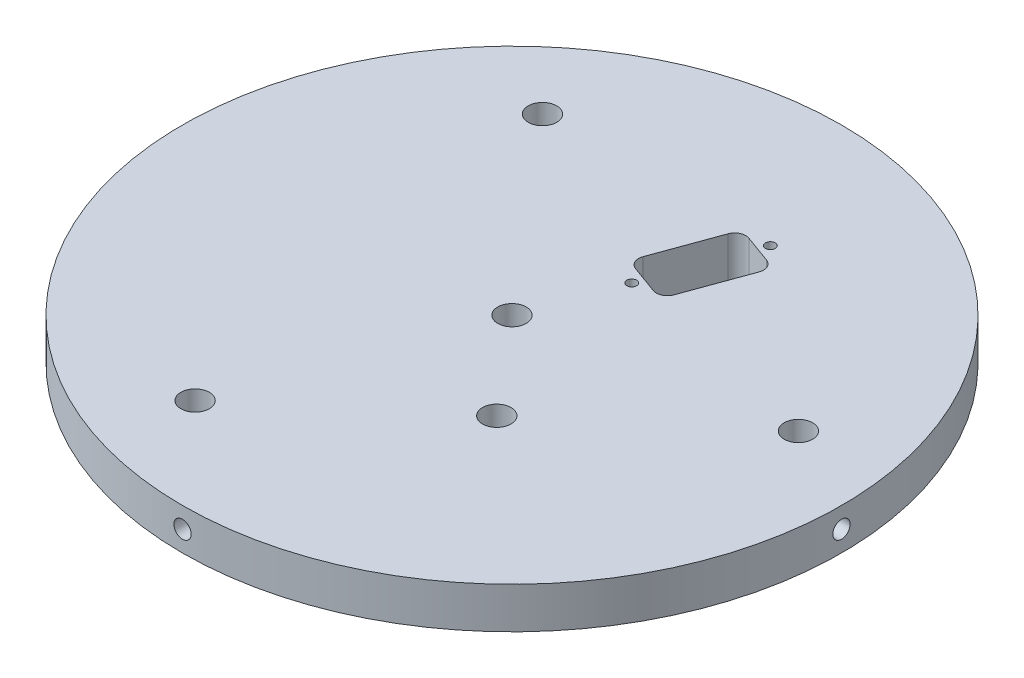
SolidWorks part; units mm, degrees
material "6061-T6 (SS)"
ref_plane "Front Plane" through (0, 0, 0) normal (0, 0, 1) x (1, 0, 0)
ref_plane "Top Plane" through (0, 0, 0) normal (0, 1, 0) x (1, 0, 0)
ref_plane "Right Plane" through (0, 0, 0) normal (1, 0, 0) x (0, 0, -1)
sketch "Sketch1" plane through (0, 0, 0) normal (0, 1, 0) x (1, 0, 0)
  line L0 (0, 0) -> (-50.3682, 60.0265)
  line L1 (0, 0) -> (50.3682, 60.0265)
  line L2 (0, 0) -> (0, 72.1431) construction
  circle A0 centre (0, 0) radius 78.359
  circle A1 centre (0, 0) radius 76.1746
  circle A2 centre (0, 0) radius 76.1746
  dimension "D1" = 156.718
  dimension "D2" = 152.3492
  dimension "D3" = 152.3492
  dimension "D4" = 80
extrude "Boss-Extrude1" add sketch "Sketch1" along normal blind 25.4 contours L2 A2 L1 A0 | L2 A1 L1 A2 | L2 A2 L1 A1 | L2 A0 L1 A2 | A2 L2 A1 L0 | A0 L2 A2 L0 | A2 L2 A0 L0 | A1 L2 A2 L0 region at (0, 0, 13.3592) region at (-23.5316, 0, -29.974) region at (-33.0764, 0, 70.9325) region at (-48.8794, 0, -59.85)
ref_plane "Plane1" through (0, 12.7, 0) normal (0, 1, 0) x (1, 0, 0)
sketch "Sketch6" plane through (0, 25.4, 0) normal (0, 1, 0) x (1, 0, 0)
  circle A0 centre (0, 0) radius 76.1746
  dimension "D1" = 152.3492
extrude "Boss-Extrude5" add sketch "Sketch6" along normal blind 9.525
sketch "Sketch7" plane through (0, 0, 0) normal (0, -1, 0) x (1, 0, 0)
  circle A0 centre (0, 0) radius 76.1746
  dimension "D1" = 152.3492
extrude "Boss-Extrude6" add sketch "Sketch7" along normal blind 9.525
sketch "Sketch8" plane through (0, -9.525, 0) normal (0, -1, 0) x (1, 0, 0)
  circle A0 centre (0, 0) radius 73.025
  dimension "D1" = 146.05
extrude "Cut-Extrude5" cut sketch "Sketch8" against normal up to surface (34.925 mm away) up to face at (0, 25.4, 76.1746)
ref_plane "Plane2" through (0, 0, -76.1746) normal (0, 0, -1) x (-1, 0, 0)
ref_plane "Plane5" through (0, 25.4, 0) normal (0, 1, 0) x (1, 0, 0)
ref_axis "Axis1" through (0, 0, 0) along (0, 1, 0)
sketch "Sketch3" plane through (0, 0, -76.1746) normal (0, 0, -1) x (-1, 0, 0)
  line L4 (76.1746, 0) -> (-76.1746, 0)
  line L5 (-76.1746, -9.525) -> (76.1746, -9.525)
  line L6 (76.1746, 25.4) -> (-76.1746, 25.4)
  line L7 (76.1746, 34.925) -> (-76.1746, 34.925)
  line L8 (0, 34.925) -> (0, 25.4) construction
  line L9 (0, 0) -> (0, -9.525) construction
  circle A0 centre (0, 30.1625) radius 2
  circle A1 centre (0, -4.7625) radius 2
  point P12 (0, 30.1625)
  point P13 (0, -4.7625)
  point P14 (-77.5445, 179.1871)
  dimension "D1" = 4
extrude "Cut-Extrude2" cut sketch "Sketch3" against normal blind 9.525 contours L8 A0 | L8 A0 | L9 A1 | L9 A1 region at (0, 30.1625, -76.1746) region at (0, -4.7625, -76.1746)
extrude "Cut-Extrude3" cut sketch "Sketch1<7>" against normal blind 9.525 from surface contours L2 A1 L1 A2 | A1 L2 A2 L0 | A2 L2 A0 L0 | L2 A2 L1 A0 region at (-23.5316, 0, -29.974) region at (-48.8794, 0, -59.85) starting at plane "Plane5"
sketch "Sketch1<7>" plane through (0, 0, 0) normal (0, 1, 0) x (1, 0, 0) same geometry as "Sketch1"
pattern_circular "CirPattern2" count 3 over 360 about axis through (0, 0, 0) along (0, 1, 0) of "Cut-Extrude3"
ref_plane "Plane3" through (0, 34.925, 0) normal (0, 1, 0) x (1, 0, 0)
sketch "Sketch4" plane through (0, 34.925, 0) normal (0, 1, 0) x (1, 0, 0)
  circle A0 centre (0, 0) radius 73.025
  dimension "D1" = 146.05
extrude "Boss-Extrude4" add sketch "Sketch4" against normal blind 9.525
pattern_circular "CirPattern3" count 4 over 360 about axis through (0, 0, 0) along (0, 1, 0) of "Cut-Extrude2"
sketch "Sketch9" plane through (0, 34.925, 0) normal (0, 1, 0) x (1, 0, 0)
  line L0 (0, 0) -> (-26.8004, -73.6334) construction
  line L1 (0, 0) -> (32.0596, -38.2071) construction
  circle A0 centre (0, 0) radius 3.3
  circle A1 centre (-19.5465, -53.7034) radius 3.3
  circle A2 centre (-36.7353, 43.7794) radius 3.3
  circle A3 centre (56.2818, 9.924) radius 3.3
  circle A4 centre (18.3677, -21.8897) radius 3.3
  point P15 (0, 0)
  dimension "D1" = 6.6
  dimension "D2" = 6.6
  dimension "D6" = 6.6
  dimension "D3" = 57.15
  dimension "D4" = 60
  dimension "D7" = 28.575
extrude "Cut-Extrude6" cut sketch "Sketch9" against normal through all
sketch "Sketch10" plane through (0, 25.4, 0) normal (0, 1, 0) x (1, 0, 0)
  circle A0 centre (0, 0) radius 82.3228
extrude "Cut-Extrude7" cut sketch "Sketch10" against normal through all
hole_wizard "Tap Drill for #4-40 Tap1" positions "Sketch12" profile "Sketch13" hole size "#4-40" standard "ANSI Inch" end condition through all
sketch "Sketch12" plane through (0, 34.925, 0) normal (0, 1, 0) x (1, 0, 0)
  line L0 (0, 0) -> (18.6243, 51.1699) construction
  line L2 (0, 0) -> (-36.7353, 43.7794) construction
  circle A0 centre (0, 0) radius 21.59 construction
  point P0 (7.3842, 20.288)
  point P2 (15.9347, 43.7803)
  dimension "D3" = 43.18
  dimension "D1" = 60
  dimension "D2" = 25
sketch "Sketch13" plane through (7.3842, 34.925, -20.288) normal (1, 0, 0) x (0, 0, 1)
  line L0 (0, 0) -> (0, 9.525)
  line L1 (0, 9.525) -> (1.1303, 9.525)
  line L2 (1.1303, 9.525) -> (1.1303, 0)
  line L5 (1.1303, 0) -> (0, 0)
  line L11 (0, -6.35) -> (0, 107.95) construction
  dimension "Thru Hole Dia." = 2.2606
  dimension "Thru Hole Depth" = 9.525
sketch "Sketch14" plane through (0, 34.925, 0) normal (0, 1, 0) x (1, 0, 0)
  line L0 (7.3842, 20.288) -> (15.9347, 43.7803) construction
  line L1 (14.6438, 22.7814) -> (19.8932, 37.2038)
  line L2 (11.3883, 21.2633) -> (4.9439, 23.6089)
  line L3 (18.3751, 40.4594) -> (11.9307, 42.8049)
  line L4 (3.4258, 26.8644) -> (8.6751, 41.2868)
  arc A0 (19.8932, 37.2038) -> (18.3751, 40.4594) centre (17.5063, 38.0725) ccw
  arc A1 (11.9307, 42.8049) -> (8.6751, 41.2868) centre (11.0619, 40.4181) ccw
  arc A2 (11.3883, 21.2633) -> (14.6438, 22.7814) centre (12.257, 23.6501) ccw
  arc A3 (4.9439, 23.6089) -> (3.4258, 26.8644) centre (5.8126, 25.9957) cw
  point P0 (8.1661, 22.4361)
  dimension "D4" = 2.54
  dimension "D5" = 2.54
  dimension "D1" = 2.286
  dimension "D2" = 2.286
  dimension "D3" = 11.938
extrude "Cut-Extrude9" cut sketch "Sketch14" against normal through all
equation "\"AB_Coupler_OD_Length\"= 1in"
equation "\"AB_Coupling_Section_Length\"= 0.375in"
equation "\"AB_Coupler_Length\"= \"AB_Coupler_OD_Length\" + \"AB_Coupling_Section_Length\" * 2"
equation "\"Cutout_Angle\" = 80"
equation "\"AB_Coupler_Num_Screws\"= 4"
equation "\"Num_Cutouts\" = 3"
equation "\"AB_Coupler_OD\"= 6.17in"
equation "\"AB_Coupler_ID\"= 5.75in"
equation "\"AB_Coupler_Surface_Diameter\"= 5.998in"
equation "\"D2@Sketch1\"=\"Bodytube_ID\""
equation "\"AB_Coupling_Screw_Diameter\"= 0.1065in"
equation "\"Aft_Section_Length\"= 39in"
equation "\"Aft_Lower_Length\"= 22in"
equation "\"Aft_Upper_Length\"= \"Aft_Section_Length\" - \"Aft_Lower_Length\" - \"AB_Coupler_OD_Length\""
equation "\"Mid_Coupler_Length\" = 13in"
equation "\"Lead_Screw_Dist\" = 3.4in"
equation "\"Lead_Screw_Diam\" = 0.386in"
equation "\"Lead_Screw_Length\" = (\"Mid_Coupler_Length\" + 2*0.375in + 2*0.5in)"
equation "\"Bodytube_OD\" = 6.17in"
equation "\"Paddle_Pin_Offset\" = .25in"
equation "\"Bodytube_ID\" = 5.998in"
equation "\"Paddle_Pin_Radius\" = 2.25in"
equation "\"D1@Sketch4\"=\"AB_Coupler_ID\""
equation "\"D1@Sketch6\"=\"AB_Coupler_Surface_Diameter\""
equation "\"D1@Boss-Extrude5\"=\"AB_Coupling_Section_Length\""
equation "\"D1@Sketch7\"=\"AB_Coupler_Surface_Diameter\""
equation "\"D1@Boss-Extrude6\"=\"AB_Coupling_Section_Length\""
equation "\"D1@Sketch8\"=\"AB_Coupler_ID\""
equation "\"D3@Sketch9\"=\"Paddle_Pin_Radius\""
equation "\"Motor_OD\" = 4in"
equation "\"Fwd_Tube_Length\" = 40in"
equation "\"Mid_Tube_Length\" = 1in"
equation "\"AB_Paddle_Height\" = 0.375in"
equation "\"AB_Central_Bushing_Length\" = .4724in"
equation "\"Paddle_Gear_OD\" = 3.2in"
equation "\"Fwd_BKHD_From_Top\" = 18in"
equation "\"Fin_Thickness\"= .118in"
equation "\"Guiderail_Cutout_Diameter\"= 1.5in"
equation "\"DB9_Hole_Dist\" = 25mm"
equation "\"D2@Sketch12\"=\"DB9_Hole_Dist\""
equation "\"Drive_Gear_OD\" = 1.7in"
equation "\"D3@Sketch12\"=\"Drive_Gear_OD\""
equation "\"DB9_Relief_Width\" = 0.47in"
equation "\"D3@Sketch14\"=\"DB9_Relief_Width\""
equation "\"DB9_Relief_Hole_Offset\" = 0.09in"
equation "\"D2@Sketch14\"=\"DB9_Relief_Hole_Offset\""
equation "\"D1@Sketch14\"=\"DB9_Relief_Hole_Offset\""
equation "\"SS_Paddle_Pin_Radius\" = 2.25*0.66in"
equation "\"Airbrakes_Wire_Hole_Dia\" = .25in"
equation "\"Airbrakes_Wire_Hole_Dist\" = 1.1in"
equation "\"Servo_Gear_Offset\" = 0.5in"
